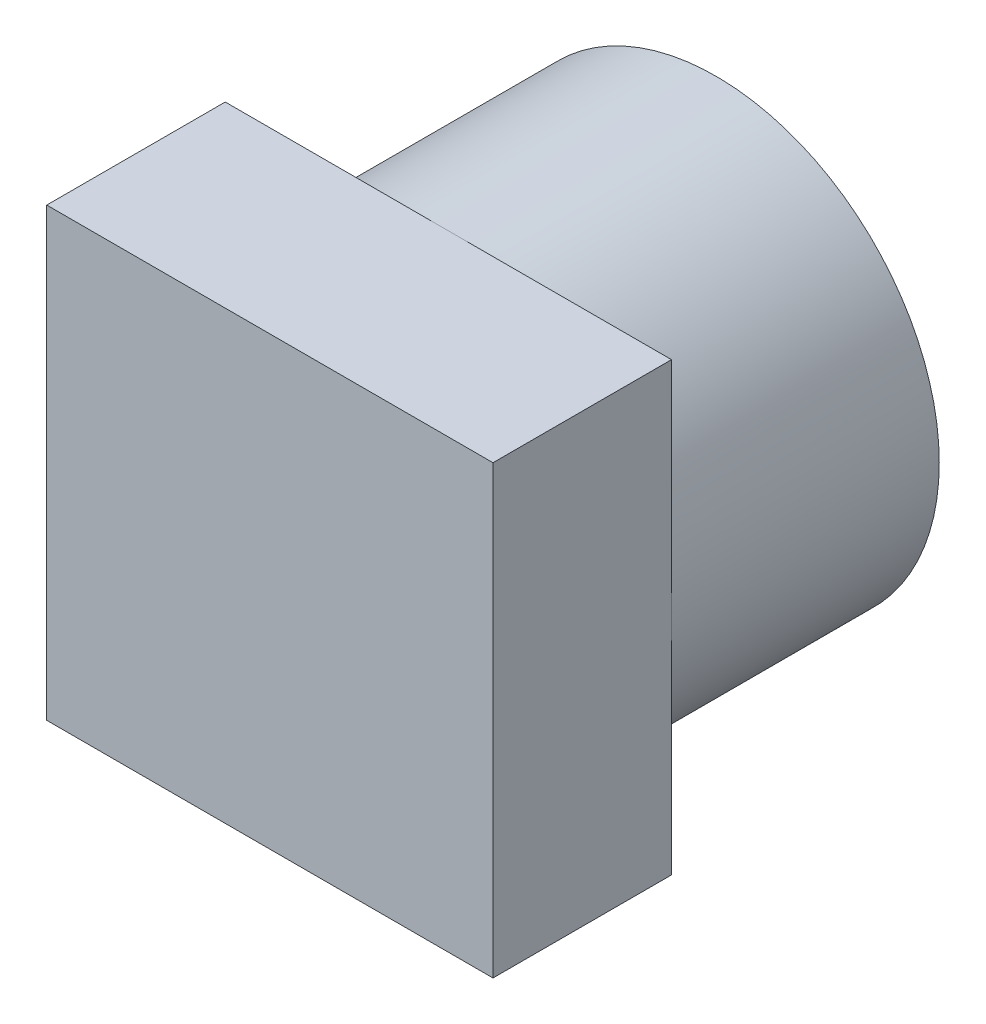
SolidWorks part; units mm, degrees
ref_plane "Front Plane" through (0, 0, 0) normal (0, 0, 1) x (1, 0, 0)
ref_plane "Top Plane" through (0, 0, 0) normal (0, 1, 0) x (1, 0, 0)
ref_plane "Right Plane" through (0, 0, 0) normal (1, 0, 0) x (0, 0, -1)
sketch "Sketch1" plane through (0, 0, 0) normal (0, 0, 1) x (1, 0, 0)
  circle A0 centre (0, 0) radius 1.25
  circle A1 centre (0, 0) radius 0.5
  dimension "D1" = 1
  dimension "D2" = 2.5
extrude "Boss-Extrude1" add sketch "Sketch1" along normal blind 1.5 contours A0
extrude "Cut-Extrude1" cut sketch "Sketch1<4>" along normal blind 1 contours A1
sketch "Sketch1<4>" plane through (0, 0, 0) normal (0, 0, 1) x (1, 0, 0) same geometry as "Sketch1"
ref_plane "Plane1" through (0, 0, 1.5) normal (0, 0, 1) x (1, 0, 0)
sketch "Sketch2" plane through (0, 0, 1.5) normal (0, 0, 1) x (1, 0, 0)
  line L0 (0, -1.25) -> (0, 1.25) construction
  line L1 (-1.25, 1.25) -> (1.25, 1.25)
  line L2 (-1.25, 1.25) -> (-1.25, -1.25)
  line L3 (-1.25, -1.25) -> (1.25, -1.25)
  line L4 (1.25, 1.25) -> (1.25, -1.25)
  line L5 (-1.25, 1.25) -> (1.25, -1.25) construction
  line L6 (-1.25, -1.25) -> (1.25, 1.25) construction
  line L7 (-1.25, 0) -> (1.25, 0) construction
  point P0 (0, 0)
  dimension "D1" = 2.5
  dimension "D2" = 2.5
extrude "Boss-Extrude2" add sketch "Sketch2" along normal blind 1
ref_plane "Plane2" through (0, 0, 2.5) normal (0, 0, 1) x (1, 0, 0)
sketch "Sketch3" plane through (0, 0, 2.5) normal (0, 0, 1) x (1, 0, 0)
  line L0 (1.25, -1.25) -> (-1.25, 1.25) construction
  line L1 (1.25, 1.25) -> (-1.25, 1.25) construction
  line L2 (-1.25, -1.25) -> (1.25, 1.25) construction
  line L3 (0, -1.25) -> (0, 1.25) construction
  line L4 (-1.25, -1.25) -> (1.25, -1.25) construction
  line L5 (-1.25, 0) -> (1.25, 0) construction
  line L6 (-1.25, 1.25) -> (-1.25, -1.25) construction
  line L7 (1.25, -1.25) -> (1.25, 1.25) construction
  point P9 (0, 0)
